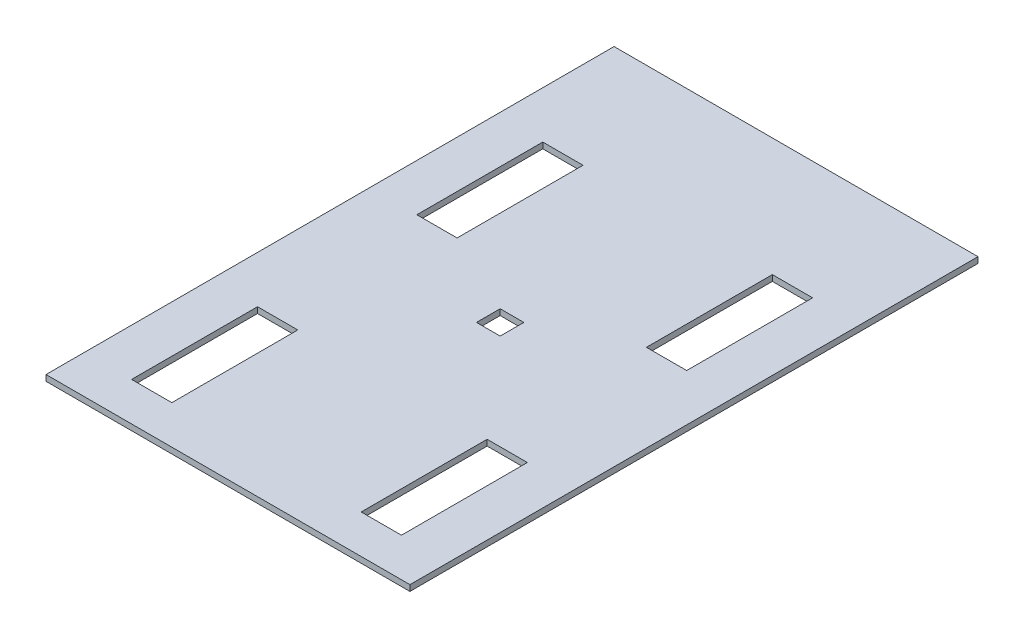
SolidWorks part; units mm, degrees
ref_plane "Front Plane" through (0, 0, 0) normal (0, 0, 1) x (1, 0, 0)
ref_plane "Top Plane" through (0, 0, 0) normal (0, 1, 0) x (1, 0, 0)
ref_plane "Right Plane" through (0, 0, 0) normal (1, 0, 0) x (0, 0, -1)
sketch "Sketch1" plane through (0, 0, 0) normal (0, 1, 0) x (1, 0, 0)
  line L1 (-195.2625, -304.8) -> (195.2625, -304.8)
  line L2 (-195.2625, -304.8) -> (-195.2625, 304.8)
  line L3 (-195.2625, 304.8) -> (195.2625, 304.8)
  line L4 (195.2625, -304.8) -> (195.2625, 304.8)
  line L5 (0, 304.8) -> (0, -304.8) construction
  line L6 (-195.2625, 0) -> (195.2625, 0) construction
  point P0 (0, 0)
  dimension "D1" = 390.525
  dimension "D2" = 609.6
extrude "Boss-Extrude1" add sketch "Sketch1" along normal blind 6.35
sketch "Sketch2" plane through (0, 6.35, 0) normal (0, 1, 0) x (1, 0, 0)
  line L0 (0, -1000) -> (0, 49000) construction
  line L5 (195.2625, 304.8) -> (-195.2625, 304.8) construction
  line L6 (101.6, -263.4234) -> (144.78, -263.4234)
  line L7 (101.6, 42.672) -> (144.78, 42.672)
  line L8 (101.6, 42.672) -> (101.6, 177.8)
  line L9 (101.6, 177.8) -> (144.78, 177.8)
  line L10 (144.78, 42.672) -> (144.78, 177.8)
  line L11 (123.19, 177.8) -> (123.19, 42.672) construction
  line L12 (101.6, 110.236) -> (144.78, 110.236) construction
  line L17 (101.6, -263.4234) -> (101.6, -128.2954)
  line L18 (101.6, -128.2954) -> (144.78, -128.2954)
  line L23 (144.78, -263.4234) -> (144.78, -128.2954)
  line L24 (123.19, -128.2954) -> (123.19, -263.4234) construction
  line L25 (101.6, -195.8594) -> (144.78, -195.8594) construction
  line L26 (-123.19, -128.2954) -> (-123.19, -263.4234) construction
  line L27 (-144.78, -263.4234) -> (-144.78, -128.2954)
  line L28 (-101.6, -263.4234) -> (-101.6, -128.2954)
  line L29 (-101.6, -263.4234) -> (-144.78, -263.4234)
  line L30 (-101.6, -195.8594) -> (-144.78, -195.8594) construction
  line L31 (-101.6, -128.2954) -> (-144.78, -128.2954)
  line L32 (-101.6, 110.236) -> (-144.78, 110.236) construction
  line L33 (-123.19, 177.8) -> (-123.19, 42.672) construction
  line L34 (-144.78, 42.672) -> (-144.78, 177.8)
  line L35 (-101.6, 177.8) -> (-144.78, 177.8)
  line L36 (-101.6, 42.672) -> (-101.6, 177.8)
  line L37 (-101.6, 42.672) -> (-144.78, 42.672)
  point P1 (123.19, -195.8594)
  point P4 (123.19, 110.236)
  point P20 (-123.19, -195.8594)
  point P29 (-123.19, 110.236)
  dimension "D1" = 135.128
  dimension "D2" = 43.18
  dimension "D3" = 135.128
  dimension "D4" = 306.0954
  dimension "D5" = 127
  dimension "D6" = 123.19
extrude "Cut-Extrude1" cut sketch "Sketch2" against normal through all
sketch "Sketch4" plane through (0, 0, 0) normal (0, 1, 0) x (1, 0, 0)
  line L5 (144.78, 177.8) -> (101.6, 177.8) construction
  line L6 (-12.7, -25.4) -> (12.7, -25.4)
  line L7 (-12.7, -25.4) -> (-12.7, 0)
  line L8 (-12.7, 0) -> (12.7, 0)
  line L9 (12.7, -25.4) -> (12.7, 0)
  line L10 (0, 0) -> (0, -25.4) construction
  line L11 (-12.7, -12.7) -> (12.7, -12.7) construction
  point P0 (0, -12.7)
  dimension "D1" = 25.4
  dimension "D2" = 177.8
  dimension "D3" = 25.4
extrude "Cut-Extrude3" cut sketch "Sketch4" along normal through all
